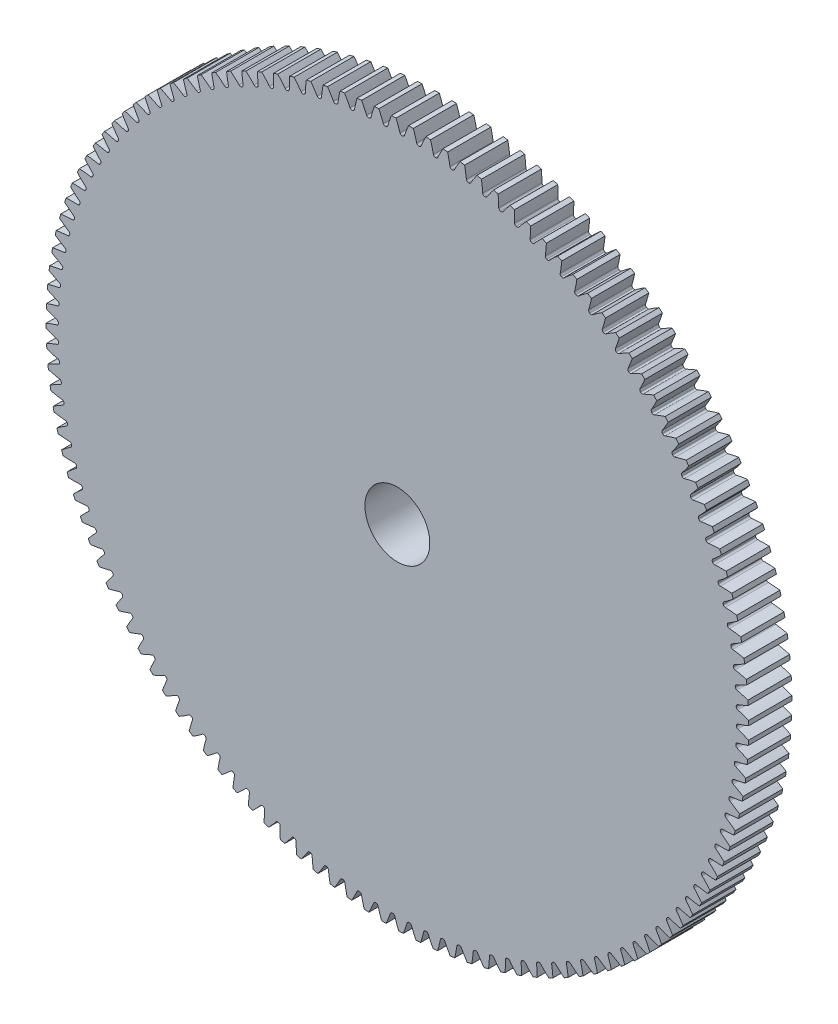
SolidWorks part; units mm, degrees
material "Delrin 2700 NC010, Low Viscosity Acetal Copolymer (SS)"
ref_plane "Front" through (0, 0, 0) normal (0, 0, 1) x (1, 0, 0)
ref_plane "Top" through (0, 0, 0) normal (0, 1, 0) x (1, 0, 0)
ref_plane "Right" through (0, 0, 0) normal (1, 0, 0) x (0, 0, -1)
sketch "Sketch3" plane through (0, 0, 0) normal (0, 0, 1) x (1, 0, 0)
  circle A0 centre (0, 0) radius 51.5938
  dimension "od" = 103.1875
extrude "gearBody" add sketch "Sketch3" along normal blind 6.35
sketch "Sketch2" plane through (0, 0, 0) normal (0, 0, 1) x (1, 0, 0)
  line L0 (0, 0) -> (44.1027, 18.2679) construction
  line L1 (60.0354, -8.954) -> (0, 0) construction
  line L2 (0, 0) -> (36.3143, 0) construction
  line L3 (50.7999, -0.1147) -> (50.7826, -1.3294) construction
  line L5 (50.7912, -0.722) -> (0, 0) construction
  line L7 (0, 0) -> (47.7364, 0) construction
  arc A0 (47.7268, -0.958) -> (47.7347, -0.399) centre (0, 0) ccw construction
  arc A1 (51.5934, 0.1942) -> (51.567, -1.6607) centre (0, 0) ccw construction
  arc A2 (50.7999, -0.1147) -> (50.7826, -1.3294) centre (0, 0) ccw construction
  arc A3 (49.7911, -0.7449) -> (49.7922, -0.6708) centre (0, 0) ccw
  arc A4 (60.0354, -8.954) -> (49.995, -1.0362) centre (43.5656, -19.5142) ccw
  arc A5 (60.0354, -8.954) -> (60.2656, 7.2438) centre (0, 0) ccw
  arc A6 (60.2656, 7.2438) -> (50.0042, -0.3853) centre (44.1027, 18.2679) cw
  arc A7 (49.7922, -0.6708) -> (50.0042, -0.3853) centre (50.0958, -0.6749) cw
  arc A8 (49.995, -1.0362) -> (49.7911, -0.7449) centre (50.0948, -0.7494) cw
  point P6 (60.2656, 7.2438)
  point P22 (60.0354, -8.954)
  dimension "baseDia" = 95.4728
  dimension "od" = 103.1875
  dimension "pd" = 101.6
  dimension "rd" = 99.5934
  dimension "rFillet" = 0.3037
  dimension "pointX" = 60.2656
  dimension "pointY" = 7.2438
  dimension "CTT" = 1.2148
  dimension "flankCenterAngle" = 22.5
extrude "toothCut" cut sketch "Sketch2" along normal through all
pattern_circular "CirPattern1" count 128 over 360 about axis through (0, 0, 6.35) along (0, 0, -1) of "toothCut"
sketch "hub1Dia" plane through (0, 0, 0) normal (0, 0, -1) x (-1, 0, 0)
  circle A0 centre (0, 0) radius 12.7
  dimension "hub1Dia" = 25.4
sketch "hub2Dia" plane through (0, 0, 6.35) normal (0, 0, 1) x (1, 0, 0)
  circle A0 centre (0, 0) radius 12.7
  dimension "hub2dia" = 25.4
sketch "boreDia" plane through (0, 0, 0) normal (0, 0, 1) x (1, 0, 0)
  circle A0 centre (0, 0) radius 1.5875
  dimension "boreDia" = 3.175
extrude "bore" cut sketch "boreDia" against normal mid plane 25400
sketch "Sketch4" plane through (0, 0, 0) normal (0, 0, -1) x (-1, 0, 0)
  arc B0 (-0.7937, -8.1656) -> (0, -11.1125) centre (2.9418, -8.7398) ccw
  arc B1 (-0.7937, -8.1656) -> (-1.303, -7.4562) centre (-1.4104, -8.0708) ccw
  arc B2 (-1.8918, -7.329) -> (-1.303, -7.4562) centre (0, 0) ccw
  arc B3 (-1.8918, -7.329) -> (-2.6485, -7.7648) centre (-2.0477, -7.9331) ccw
  arc B4 (-4.5881, -10.1211) -> (-2.6485, -7.7648) centre (-6.2878, -6.7454) ccw
  arc B5 (-4.7702, -6.6747) -> (-5.5563, -9.6237) centre (-1.8222, -9.0398) ccw
  arc B6 (-4.7702, -6.6747) -> (-4.8565, -5.8058) centre (-5.2568, -6.2843) ccw
  arc B7 (-5.3028, -5.4012) -> (-4.8565, -5.8058) centre (0, 0) ccw
  arc B8 (-5.3028, -5.4012) -> (-6.176, -5.4003) centre (-5.7399, -5.8464) ccw
  arc B9 (-9.034, -6.4711) -> (-6.176, -5.4003) centre (-8.8182, -2.6978) ccw
  arc B10 (-7.4685, -3.3954) -> (-9.6237, -5.5562) centre (-6.098, -6.9176) ccw
  arc B11 (-7.4685, -3.3954) -> (-7.1088, -2.5997) centre (-7.6947, -2.814) ccw
  arc B12 (-7.293, -2.0262) -> (-7.1088, -2.5997) centre (0, 0) ccw
  arc B13 (-7.293, -2.0262) -> (-8.0487, -1.5888) centre (-7.8941, -2.1932) ccw
  arc B14 (-11.0592, -1.0871) -> (-8.0487, -1.5888) centre (-8.9856, 2.0727) ccw
  arc B15 (-8.1656, 0.7937) -> (-11.1125, 0) centre (-8.7398, -2.9418) ccw
  arc B16 (-8.1656, 0.7937) -> (-7.4562, 1.303) centre (-8.0708, 1.4104) ccw
  arc B17 (-7.329, 1.8918) -> (-7.4562, 1.303) centre (0, 0) ccw
  arc B18 (-7.329, 1.8918) -> (-7.7648, 2.6485) centre (-7.9331, 2.0477) ccw
  arc B19 (-10.1211, 4.5881) -> (-7.7648, 2.6485) centre (-6.7454, 6.2878) ccw
  arc B20 (-6.6747, 4.7702) -> (-9.6237, 5.5563) centre (-9.0398, 1.8222) ccw
  arc B21 (-6.6747, 4.7702) -> (-5.8058, 4.8565) centre (-6.2843, 5.2568) ccw
  arc B22 (-5.4012, 5.3028) -> (-5.8058, 4.8565) centre (0, 0) ccw
  arc B23 (-5.4012, 5.3028) -> (-5.4003, 6.176) centre (-5.8464, 5.7399) ccw
  arc B24 (-6.4711, 9.034) -> (-5.4003, 6.176) centre (-2.6978, 8.8182) ccw
  arc B25 (-3.3954, 7.4685) -> (-5.5563, 9.6237) centre (-6.9176, 6.098) ccw
  arc B26 (-3.3954, 7.4685) -> (-2.5997, 7.1088) centre (-2.814, 7.6947) ccw
  arc B27 (-2.0262, 7.293) -> (-2.5997, 7.1088) centre (0, 0) ccw
  arc B28 (-2.0262, 7.293) -> (-1.5888, 8.0487) centre (-2.1932, 7.8941) ccw
  arc B29 (-1.0871, 11.0592) -> (-1.5888, 8.0487) centre (2.0727, 8.9856) ccw
  arc B30 (0.7937, 8.1656) -> (0, 11.1125) centre (-2.9418, 8.7398) ccw
  arc B31 (0.7937, 8.1656) -> (1.303, 7.4562) centre (1.4104, 8.0708) ccw
  arc B32 (1.8918, 7.329) -> (1.303, 7.4562) centre (0, 0) ccw
  arc B33 (1.8918, 7.329) -> (2.6485, 7.7648) centre (2.0477, 7.9331) ccw
  arc B34 (4.5881, 10.1211) -> (2.6485, 7.7648) centre (6.2878, 6.7454) ccw
  arc B35 (4.7702, 6.6747) -> (5.5562, 9.6237) centre (1.8222, 9.0398) ccw
  arc B36 (4.7702, 6.6747) -> (4.8565, 5.8058) centre (5.2568, 6.2843) ccw
  arc B37 (5.3028, 5.4012) -> (4.8565, 5.8058) centre (0, 0) ccw
  arc B38 (5.3028, 5.4012) -> (6.176, 5.4003) centre (5.7399, 5.8464) ccw
  arc B39 (9.034, 6.4711) -> (6.176, 5.4003) centre (8.8182, 2.6978) ccw
  arc B40 (7.4685, 3.3954) -> (9.6237, 5.5562) centre (6.098, 6.9176) ccw
  arc B41 (7.4685, 3.3954) -> (7.1088, 2.5997) centre (7.6947, 2.814) ccw
  arc B42 (7.293, 2.0262) -> (7.1088, 2.5997) centre (0, 0) ccw
  arc B43 (7.293, 2.0262) -> (8.0487, 1.5888) centre (7.8941, 2.1932) ccw
  arc B44 (11.0592, 1.0871) -> (8.0487, 1.5888) centre (8.9856, -2.0727) ccw
  arc B45 (8.1656, -0.7937) -> (11.1125, 0) centre (8.7398, 2.9418) ccw
  arc B46 (8.1656, -0.7937) -> (7.4562, -1.303) centre (8.0708, -1.4104) ccw
  arc B47 (7.329, -1.8918) -> (7.4562, -1.303) centre (0, 0) ccw
  arc B48 (7.329, -1.8918) -> (7.7648, -2.6485) centre (7.9331, -2.0477) ccw
  arc B49 (10.1211, -4.5881) -> (7.7648, -2.6485) centre (6.7454, -6.2878) ccw
  arc B50 (6.6747, -4.7702) -> (9.6237, -5.5563) centre (9.0398, -1.8222) ccw
  arc B51 (6.6747, -4.7702) -> (5.8058, -4.8565) centre (6.2843, -5.2568) ccw
  arc B52 (5.4012, -5.3028) -> (5.8058, -4.8565) centre (0, 0) ccw
  arc B53 (5.4012, -5.3028) -> (5.4003, -6.176) centre (5.8464, -5.7399) ccw
  arc B54 (6.4711, -9.034) -> (5.4003, -6.176) centre (2.6978, -8.8182) ccw
  arc B55 (3.3954, -7.4685) -> (5.5562, -9.6237) centre (6.9176, -6.098) ccw
  arc B56 (3.3954, -7.4685) -> (2.5997, -7.1088) centre (2.814, -7.6947) ccw
  arc B57 (2.0262, -7.293) -> (2.5997, -7.1088) centre (0, 0) ccw
  arc B58 (2.0262, -7.293) -> (1.5888, -8.0487) centre (2.1932, -7.8941) ccw
  arc B59 (1.0871, -11.0592) -> (1.5888, -8.0487) centre (-2.0727, -8.9856) ccw
  arc B60 (0, -11.1125) -> (1.0871, -11.0592) centre (0, 0) ccw
  arc B61 (9.6237, -5.5563) -> (10.1211, -4.5881) centre (0, 0) ccw
  arc B62 (11.1125, 0) -> (11.0592, 1.0871) centre (0, 0) ccw
  arc B63 (9.6237, 5.5562) -> (9.034, 6.4711) centre (0, 0) ccw
  arc B64 (5.5562, 9.6237) -> (4.5881, 10.1211) centre (0, 0) ccw
  arc B65 (0, 11.1125) -> (-1.0871, 11.0592) centre (0, 0) ccw
  arc B66 (-5.5563, 9.6237) -> (-6.4711, 9.034) centre (0, 0) ccw
  arc B67 (-9.6237, 5.5563) -> (-10.1211, 4.5881) centre (0, 0) ccw
  arc B68 (-11.1125, 0) -> (-11.0592, -1.0871) centre (0, 0) ccw
  arc B69 (-9.6237, -5.5562) -> (-9.034, -6.4711) centre (0, 0) ccw
  arc B70 (-5.5563, -9.6237) -> (-4.5881, -10.1211) centre (0, 0) ccw
  arc B71 (5.5562, -9.6237) -> (6.4711, -9.034) centre (0, 0) ccw
sketch_block_instance "Block1-1"
sketch_block "Block1"
extrude "Boss-Extrude1" add sketch "Sketch4" along normal blind 19.05
hole_wizard "3/8 (0.375) Diameter Hole1" positions "Sketch6" profile "Sketch8" hole size "3/8" standard "ANSI Inch" end condition through all
sketch "Sketch6" plane through (0, 0, -19.05) normal (0, 0, -1) x (-1, 0, 0)
  point P0 (0, 0)
sketch "Sketch8" plane through (0, 0, -19.05) normal (1, 0, 0) x (0, 1, 0)
  line L0 (0, 0) -> (0, 25.4)
  line L1 (0, 25.4) -> (4.7625, 25.4)
  line L2 (4.7625, 25.4) -> (4.7625, 0)
  line L5 (4.7625, 0) -> (0, 0)
  line L11 (0, -6.35) -> (0, 107.95) construction
  dimension "Thru Hole Dia." = 9.525
  dimension "Thru Hole Depth" = 25.4
